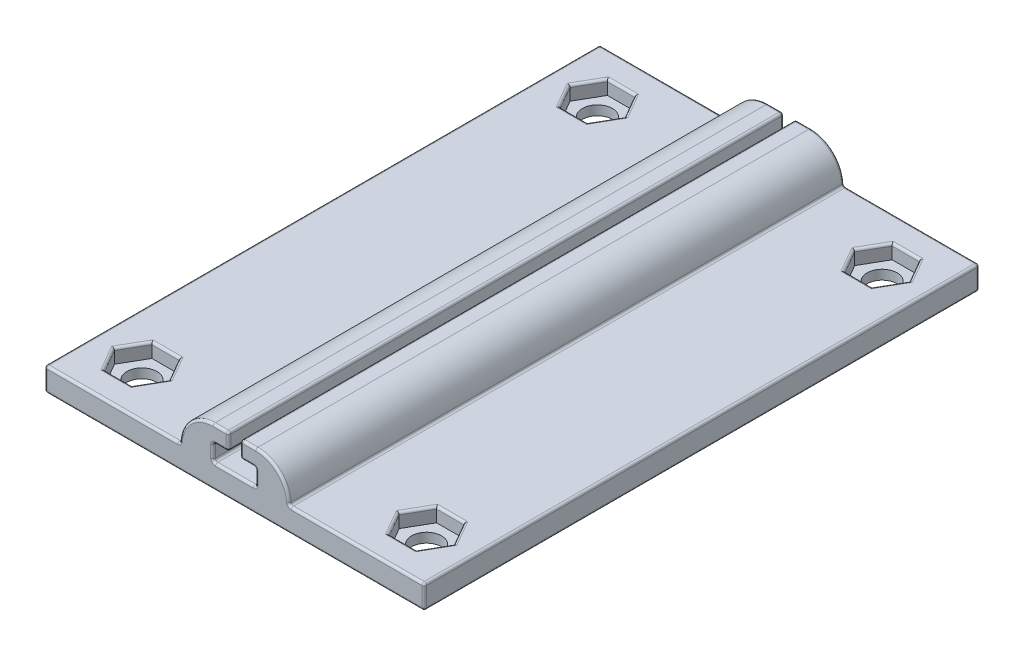
SolidWorks part; units mm, degrees
ref_plane "Front Plane" through (0, 0, 0) normal (0, 0, 1) x (1, 0, 0)
ref_plane "Top Plane" through (0, 0, 0) normal (0, 1, 0) x (1, 0, 0)
ref_plane "Right Plane" through (0, 0, 0) normal (1, 0, 0) x (0, 0, -1)
sketch "Sketch1" plane through (0, 0, 0) normal (0, 0, 1) x (1, 0, 0)
  line L0 (0, -28.2286) -> (0, 28.2286) construction
  line L1 (-40, -2.5) -> (40, -2.5)
  line L2 (-40, -2.5) -> (-40, 2.5)
  line L3 (-40, 2.5) -> (-11.5, 2.5)
  line L4 (40, -2.5) -> (40, 2.5)
  line L5 (-40, -2.5) -> (40, 2.5) construction
  line L6 (-40, 2.5) -> (40, -2.5) construction
  line L7 (-4.5, 2.5) -> (4.5, 2.5)
  line L8 (0, 2.5) -> (-4.5, 2.5) construction
  line L9 (0, 2.5) -> (0, 6) construction
  line L10 (0, 6) -> (-4.5, 6) construction
  line L12 (0, 6) -> (-1.25, 6) construction
  line L13 (0, 6) -> (0, 16.858) construction
  line L14 (0, 16.858) -> (-1.25, 16.858) construction
  line L15 (-1.25, 6) -> (-1.25, 16.858) construction
  line L16 (-4.5, 6) -> (-1.25, 6)
  line L17 (-4.5, 2.5) -> (-4.5, 6)
  line L18 (-4.5, 9.5) -> (-1.25, 9.5)
  line L19 (-1.25, 6) -> (-1.25, 9.5)
  line L20 (4.5, 2.5) -> (4.5, 6)
  line L21 (1.25, 6) -> (1.25, 9.5)
  line L22 (4.5, 6) -> (1.25, 6)
  line L23 (4.5, 9.5) -> (1.25, 9.5)
  line L24 (11.5, 2.5) -> (40, 2.5)
  arc A0 (-4.5, 9.5) -> (-11.5, 2.5) centre (-4.5, 2.5) ccw
  arc A1 (4.5, 9.5) -> (11.5, 2.5) centre (4.5, 2.5) cw
  point P0 (0, 0)
  point P9 (0, 0)
  dimension "D1" = 80
  dimension "D2" = 5
  dimension "D3" = 3.5
  dimension "D4" = 4.5
  dimension "D5" = 1.25
  dimension "D6" = 3.5
extrude "Boss-Extrude1" add sketch "Sketch1" along normal blind 58.5 and the other way blind 58.5 contours L7 L20 L22 L21 L23 A1 L24 L4 L1 L2 L3 A0 L18 L19 L16 L17
sketch "Sketch2" plane through (0, -2.5, 0) normal (0, -1, 0) x (1, 0, 0)
  line L0 (0, -58.5) -> (0, -52) construction
  line L2 (-40, -58.5) -> (40, -58.5) construction
  line L3 (0, 58.5) -> (0, 48) construction
  line L4 (-40, 58.5) -> (40, 58.5) construction
  line L5 (0, 48) -> (-30, 48) construction
  circle A0 centre (-30, 48) radius 3.15
  circle A1 centre (30, 48) radius 3.15
  circle A2 centre (30, -48) radius 3.15
  circle A3 centre (-30, -48) radius 3.15
  point P6 (0, 0)
  dimension "D4" = 6.3
  dimension "D1" = 10.5
  dimension "D2" = 6.5
  dimension "D3" = 30
  dimension "D5" = 2
  dimension "D6" = 2
extrude "Cut-Extrude1" cut sketch "Sketch2" against normal blind 58.5
fillet "Fillet1" radius 0.5 50 edges at (40, -2.5, 0) (-40, -2.5, 0) (-4.5, 6, 0) (-1.25, 6, 0) (-1.25, 9.5, 0) (1.25, 9.5, 0) (1.25, 6, 0) (4.5, 6, 0) (4.5, 2.5, 0) (-4.5, 2.5, 0) (-2.875, 6, -58.5) (-1.25, 7.75, -58.5) (-2.875, 9.5, -58.5) (-9.4497, 7.4497, -58.5) (-40, 0, -58.5) (0, -2.5, -58.5) (40, 0, -58.5) (9.4497, 7.4497, -58.5) (2.875, 9.5, -58.5) (1.25, 7.75, -58.5) (2.875, 6, -58.5) (4.5, 4.25, -58.5) (0, 2.5, -58.5) (-4.5, 4.25, -58.5) (0, 2.5, 58.5) (4.5, 4.25, 58.5) (2.875, 6, 58.5) (1.25, 7.75, 58.5) (2.875, 9.5, 58.5) (9.4497, 7.4497, 58.5) (40, 0, 58.5) (0, -2.5, 58.5) (-40, 0, 58.5) (-9.4497, 7.4497, 58.5) (-2.875, 9.5, 58.5) (-1.25, 7.75, 58.5) (-2.875, 6, 58.5) (-4.5, 4.25, 58.5) (-25.75, 2.5, -58.5) (-11.5, 2.5, 0) (-25.75, 2.5, 58.5) (-40, 2.5, 0) (-30, 2.5, -51.15) (-30, 2.5, 44.85) (25.75, 2.5, -58.5) (40, 2.5, 0) (25.75, 2.5, 58.5) (11.5, 2.5, 0) (33.15, 2.5, 48) (33.15, 2.5, -48)
sketch "Sketch3" plane through (0, 2.5, 0) normal (0, 1, 0) x (1, 0, 0)
  line L1 (-24.2265, 48) -> (-27.1132, 53)
  line L2 (-27.1132, 53) -> (-32.8868, 53)
  line L3 (-32.8868, 53) -> (-35.7735, 48)
  line L4 (-35.7735, 48) -> (-32.8868, 43)
  line L5 (-32.8868, 43) -> (-27.1132, 43)
  line L6 (-27.1132, 43) -> (-24.2265, 48)
  line L7 (-24.2265, -48) -> (-27.1132, -43)
  line L8 (-27.1132, -43) -> (-32.8868, -43)
  line L9 (-32.8868, -43) -> (-35.7735, -48)
  line L10 (-35.7735, -48) -> (-32.8868, -53)
  line L11 (-32.8868, -53) -> (-27.1132, -53)
  line L12 (-27.1132, -53) -> (-24.2265, -48)
  circle A0 centre (-30, 48) radius 5 construction
  circle A1 centre (-30, -48) radius 5 construction
  dimension "D1" = 10
  dimension "D2" = 10
extrude "Cut-Extrude2" cut sketch "Sketch3" against normal blind 3
pattern_linear "LPattern1" count 2 spacing 60 along (1, 0, 0) of "Cut-Extrude2"
fillet "Fillet2" radius 0.5 24 edges at (30, 2.5, 43) (25.6699, 2.5, 45.5) (25.6699, 2.5, 50.5) (30, 2.5, 53) (34.3301, 2.5, 50.5) (34.3301, 2.5, 45.5) (30, 2.5, -53) (25.6699, 2.5, -50.5) (25.6699, 2.5, -45.5) (30, 2.5, -43) (34.3301, 2.5, -45.5) (34.3301, 2.5, -50.5) (-30, 2.5, 43) (-34.3301, 2.5, 45.5) (-34.3301, 2.5, 50.5) (-30, 2.5, 53) (-25.6699, 2.5, 50.5) (-25.6699, 2.5, 45.5) (-30, 2.5, -53) (-34.3301, 2.5, -50.5) (-34.3301, 2.5, -45.5) (-30, 2.5, -43) (-25.6699, 2.5, -45.5) (-25.6699, 2.5, -50.5)
